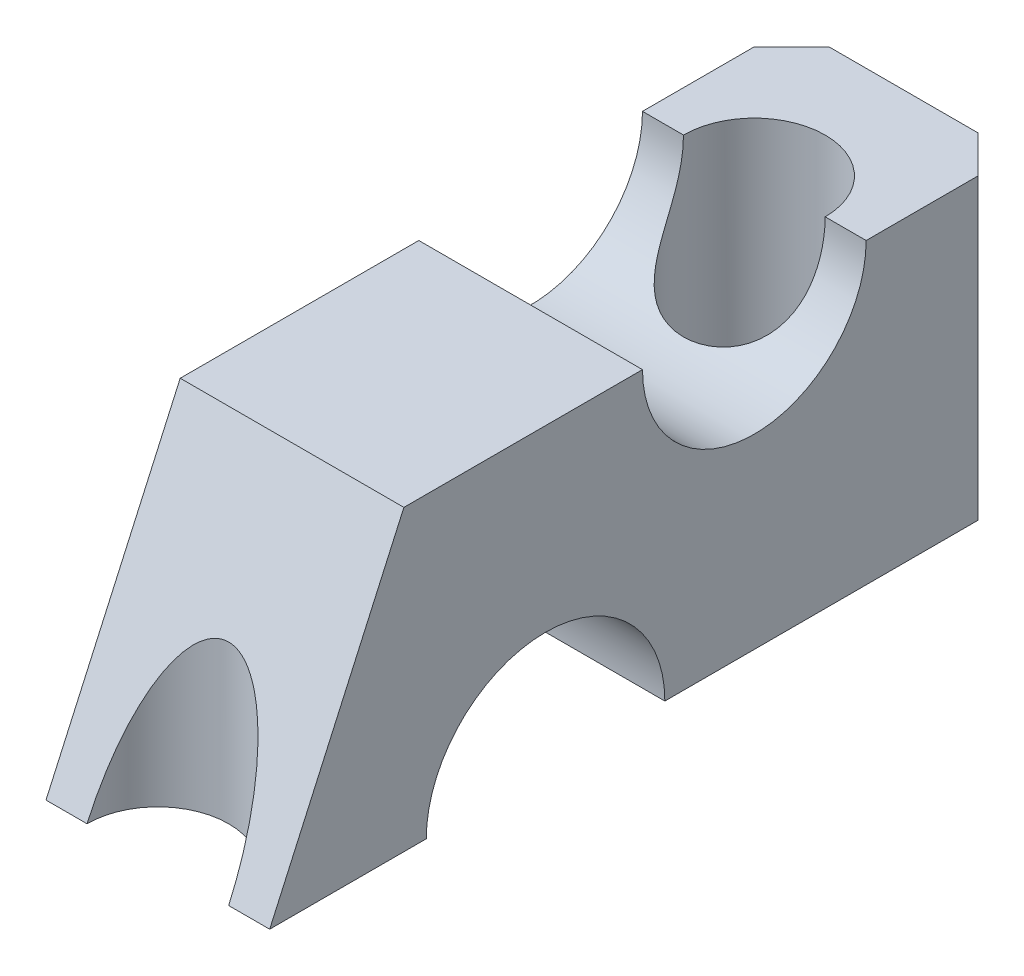
SolidWorks part; units mm, degrees
ref_plane "Alzado" through (0, 0, 0) normal (0, 0, 1) x (1, 0, 0)
ref_plane "Planta" through (0, 0, 0) normal (0, 1, 0) x (1, 0, 0)
ref_plane "Vista lateral" through (0, 0, 0) normal (1, 0, 0) x (0, 0, -1)
sketch "Croquis1" plane through (0, 0, 0) normal (1, 0, 0) x (0, 0, -1)
  line L0 (-100, 0) -> (-82, 40)
  line L1 (0, 0) -> (-100, 0)
  line L2 (0, 0) -> (0, 40)
  line L3 (0, 40) -> (-82, 40)
  dimension "D1" = 40
  dimension "D2" = 100
  dimension "D3" = 82
extrude "Saliente-Extruir1" add sketch "Croquis1" along normal blind 30
sketch "Croquis2" plane through (0, 40, 0) normal (0, 1, 0) x (1, 0, 0)
  line L0 (30, -100) -> (0, -100) construction
  line L1 (30, 0) -> (0, 0) construction
  circle A0 centre (15, -100) radius 9.5
  circle A1 centre (15, -20) radius 9.5
  point P9 (15, 0)
  dimension "D1" = 19
  dimension "D2" = 19
  dimension "D3" = 20
extrude "Cortar-Extruir1" cut sketch "Croquis2" against normal blind 94 and the other way blind 54
sketch "Croquis3" plane through (30, 0, 0) normal (1, 0, 0) x (0, 0, -1)
  line L0 (0, 40) -> (-82, 40) construction
  line L1 (0, 0) -> (0, 40) construction
  line L2 (-100, 0) -> (0, 0) construction
  circle A0 centre (-35, 40) radius 15
  circle A1 centre (-63, 0) radius 16
  dimension "D1" = 30
  dimension "D3" = 32
  dimension "D2" = 35
  dimension "D4" = 63
extrude "Cortar-Extruir2" cut sketch "Croquis3" against normal blind 94 and the other way blind 94
chamfer "Chaflán1" distance 5 angle 45 2 edges at (0, 20, 0) (30, 20, 0)
